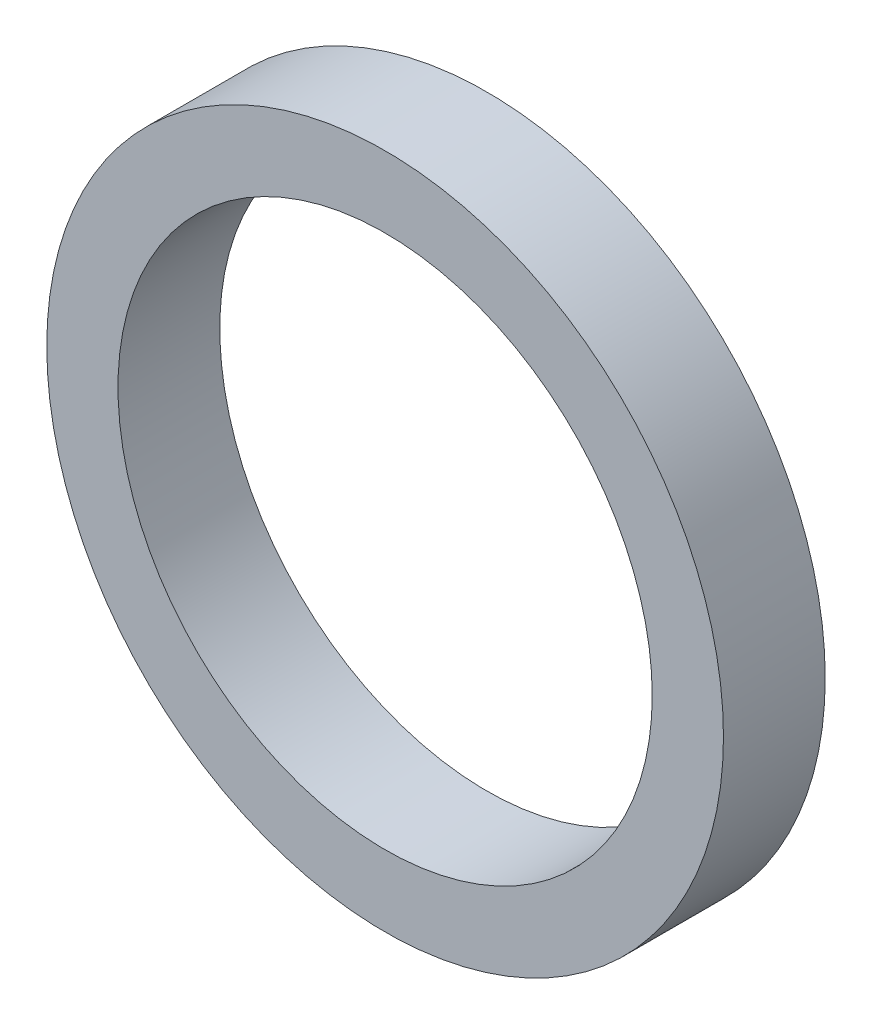
SolidWorks part; units mm, degrees
material "ABS"
ref_plane "Front Plane" through (0, 0, 0) normal (0, 0, 1) x (1, 0, 0)
ref_plane "Top Plane" through (0, 0, 0) normal (0, 1, 0) x (1, 0, 0)
ref_plane "Right Plane" through (0, 0, 0) normal (1, 0, 0) x (0, 0, -1)
sketch "Sketch1" plane through (0, 0, 3) normal (0, 0, 1) x (1, 0, 0)
  circle A0 centre (32.5, 0) radius 2.625
  circle A1 centre (32.5, 0) radius 3.325
  dimension "D1" = 5.25
  dimension "D2" = 6.65
extrude "Boss-Extrude1" add sketch "Sketch1" along normal blind 1
equation "\"RingPinShaft\"= 5.05"
equation "\"CenterBearingOut\"=32.00"
equation "\"OutputBearingOut\"=50.00"
equation "\"RingPostIn\"=5.15"
equation "\"CamBearingOut\"=15.1"
equation "\"DiskOutputShaft\"=10.1"
equation "\"CenterShaft\"=25.2"
equation "\"Eccentricity\"=2"
equation "\"CycCamShaft\"=10.05"
equation "\"m3Thru\"=3.15"
equation "\"m3Insert\"=4.2"
equation "\"D1@Sketch1\"=\"RingPostIn\"+0.1"
equation "\"D2@Sketch1\"=\"RingPostIn\"+1.5"
